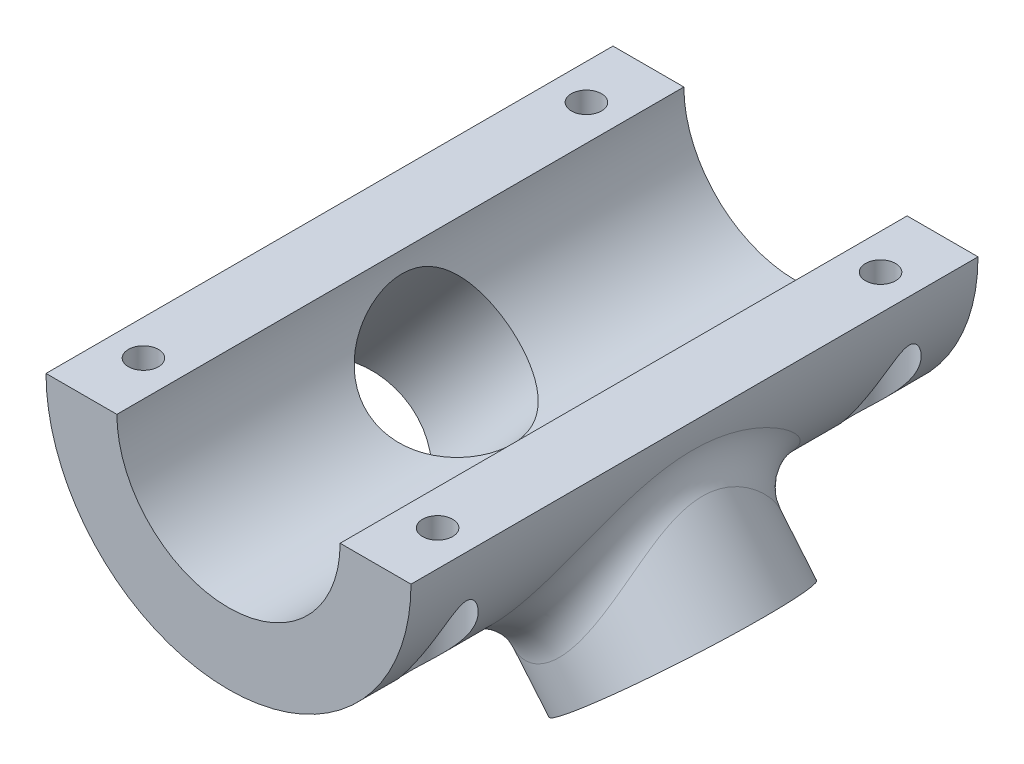
SolidWorks part; units mm, degrees
note: The reader was unsure of these and kept them because the rebuilt part matched: shared geometry of "Sketch4<3>".
material "ABS"
ref_plane "Front Plane" through (0, 0, 0) normal (0, 0, 1) x (1, 0, 0)
ref_plane "Top Plane" through (0, 0, 0) normal (0, 1, 0) x (1, 0, 0)
ref_plane "Right Plane" through (0, 0, 0) normal (1, 0, 0) x (0, 0, -1)
sketch "Sketch1" plane through (0, 0, 0) normal (0, 0, 1) x (1, 0, 0)
  line L0 (-20.6, 0) -> (-12.6, 0)
  line L1 (12.6, 0) -> (20.6, 0)
  line L2 (-16.6, 0) -> (-16.6, -29693.8434) construction
  line L3 (16.6, 0) -> (16.6, -29693.8434) construction
  arc A2 (12.6, 0) -> (-12.6, 0) centre (0, 0) cw
  arc A3 (20.6, 0) -> (-20.6, 0) centre (0, 0) cw
  point P10 (-16.6, 0)
  point P13 (16.6, 0)
  dimension "D1" = 25.2
  dimension "D2" = 4
extrude "Boss-Extrude1" add sketch "Sketch1" along normal mid plane 64
sketch "Sketch2" plane through (0, 0, 0) normal (0, 1, 0) x (1, 0, 0)
  line L1 (-16.6, -25) -> (16.6, -25)
  line L2 (-16.6, -25) -> (-16.6, 25)
  line L3 (-16.6, 25) -> (16.6, 25)
  line L4 (16.6, -25) -> (16.6, 25)
  line L5 (-16.6, -25) -> (16.6, 25) construction
  line L6 (-16.6, 25) -> (16.6, -25) construction
  point P0 (0, 0)
  point P6 (16.6, 0)
  point P7 (-16.6, 25)
  point P10 (16.6, 25)
  point P11 (16.6, -25)
  point P12 (-16.6, -25)
  dimension "D1" = 50
hole_wizard "CBORE for M3 SHCS1" positions "Sketch2" profile "Sketch3" counterbore size "M3" standard "ANSI Metric"
sketch "Sketch3" plane through (-16.6, 0, 25) normal (1, 0, 0) x (0, 0, 1)
  line L0 (0, 0) -> (0, 20.6)
  line L1 (0, 20.6) -> (3.25, 20.6)
  line L3 (3.25, 20.6) -> (3.25, 3)
  line L4 (3.25, 3) -> (1.7, 3)
  line L5 (1.7, 3) -> (1.7, 0)
  line L7 (1.7, 0) -> (0, 0)
  line L11 (0, -6.35) -> (0, 107.95) construction
  dimension "Thru Hole Dia." = 6.5
  dimension "Thru Hole Depth" = 20.6
  dimension "C'Bore Dia." = 3.4
  dimension "C'Bore Depth" = 3
sketch "Sketch4" plane through (0, 0, 0) normal (0, 0, 1) x (1, 0, 0)
  line L0 (-10.3298, -12.3106) -> (-19.2836, -22.9813)
  line L1 (10.3298, -12.3106) -> (19.2836, -22.9813)
  line L2 (-10.3298, -12.3106) -> (0, 0) construction
  line L3 (0, 0) -> (10.3298, -12.3106) construction
  dimension "D1" = 80
  dimension "D2" = 30
sweep "Sweep1" add path "Sketch4" circular profile diameter 24 parameters "D3"=24
sweep "Sweep2" add path "Sketch4<3>" circular profile diameter 24 parameters "D3"=24
sketch "Sketch4<3>" plane through (0, 0, 0) normal (0, 0, 1) x (1, 0, 0) same geometry as "Sketch4"
sketch "Sketch22" plane through (19.2836, -22.9813, 0) normal (0.6428, -0.766, 0) x (0, 0, -1)
  circle A0 centre (0, 0) radius 8.125
  dimension "D1" = 16.25
extrude "Cut-Extrude1" cut sketch "Sketch22" against normal blind 30
sketch "Sketch23" plane through (-19.2836, -22.9813, 0) normal (-0.6428, -0.766, 0) x (0, 0, 1)
  circle A0 centre (0, 0) radius 8.125
  dimension "D1" = 16.25
extrude "Cut-Extrude2" cut sketch "Sketch23" against normal blind 30
sketch "Sketch25" plane through (0, 0, 0) normal (0, 1, 0) x (1, 0, 0)
  line L1 (-10, -1.5) -> (10, -1.5)
  line L2 (-10, -1.5) -> (-10, 1.5)
  line L3 (-10, 1.5) -> (10, 1.5)
  line L4 (10, -1.5) -> (10, 1.5)
  line L5 (-10, -1.5) -> (10, 1.5) construction
  line L6 (-10, 1.5) -> (10, -1.5) construction
  point P0 (0, 0)
  dimension "D1" = 3
  dimension "D2" = 20
extrude "Boss-Extrude2" add sketch "Sketch25" along normal up to body from offset 30 offset against normal yes
fillet "Fillet1" radius 5 8 edges at (-19.9551, -5.1141, 0.1408) (5.6582, -25.2655, -1.5) (0, -20.6, -1.5) (-5.6582, -25.2655, -1.5) (-5.6582, -25.2655, 1.5) (0, -20.6, 1.5) (5.6582, -25.2655, 1.5)
equation "\"6omm\"=75"
